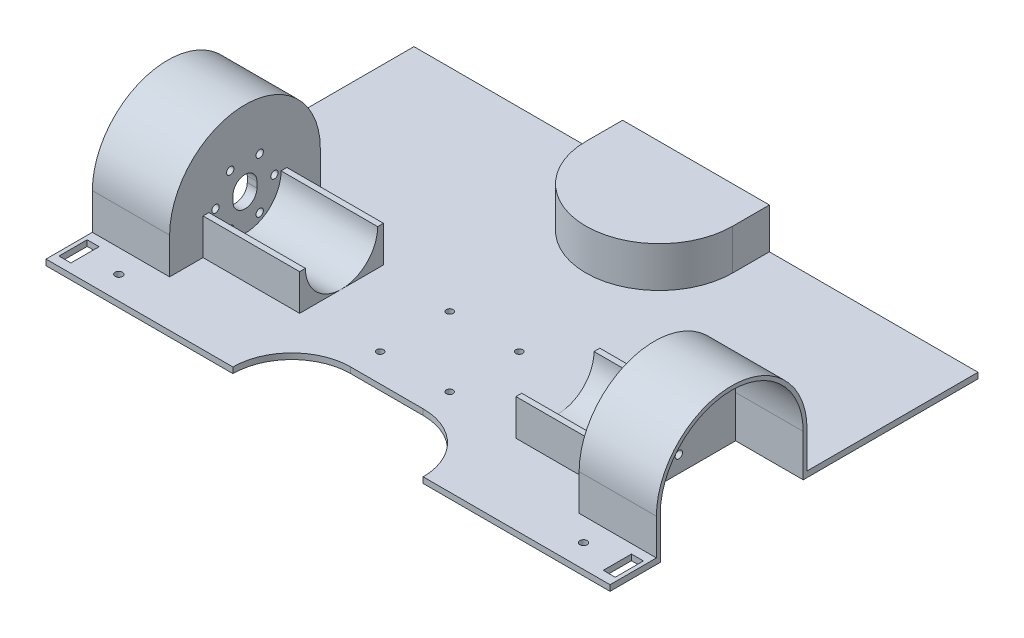
SolidWorks part; units mm, degrees
ref_plane "Front Plane" through (0, 0, 0) normal (0, 0, 1) x (1, 0, 0)
ref_plane "Top Plane" through (0, 0, 0) normal (0, 1, 0) x (1, 0, 0)
ref_plane "Right Plane" through (0, 0, 0) normal (1, 0, 0) x (0, 0, -1)
sketch3d "3DSketch1"
  line L0 (-150, -15, 34.5) -> (150, -15, 34.5) construction
  line L1 (150, -15, 34.5) -> (150, -15, -165.5) construction
  line L2 (150, -15, -165.5) -> (-150, -15, -165.5) construction
  line L3 (-150, -15, -165.5) -> (-150, -15, 34.5) construction
  line L4 (-150, -15, 34.5) -> (-150, 185, 34.5) construction
  line L5 (-150, 185, 34.5) -> (150, 185, 34.5) construction
  line L6 (150, 185, 34.5) -> (150, -15, 34.5) construction
  line L7 (0, -15, 0) -> (0, -15, 34.5) construction
  line L8 (150, 185, 34.5) -> (150, 185, -165.5) construction
  line L9 (150, 185, -165.5) -> (150, -15, -165.5) construction
  line L10 (150, 185, -165.5) -> (-150, 185, -165.5) construction
  line L11 (-150, 185, -165.5) -> (-150, -15, -165.5) construction
  line L12 (-150, 185, -165.5) -> (-150, 185, 34.5) construction
  line L13 (0, -15, 0) -> (0, 0, 0) construction
  dimension "D5" = 15
  dimension "D1" = 34.5
  dimension "D2" = 300
  dimension "D3" = 200
  dimension "D4" = 200
sketch "Sketch2" plane through (0, 0, 0) normal (0, 1, 0) x (1, 0, 0)
  line L0 (-146, 0) -> (146, 0)
  line L1 (146, 0) -> (146, 160)
  line L2 (146, 160) -> (-146, 160)
  line L3 (150, -34.5) -> (150, 165.5) construction
  line L4 (-146, 160) -> (-146, 0)
  line L5 (150, 165.5) -> (-150, 165.5) construction
  point P4 (0, 0)
  point P11 (0, 0)
  dimension "D1" = 4
  dimension "D2" = 5.5
extrude "Boss-Extrude1" add sketch "Sketch2" along normal blind 3
sketch "Sketch3" plane through (0, 3, 0) normal (0, 1, 0) x (1, 0, 0)
  line L0 (146, 0) -> (146, -30.5)
  line L1 (146, -30.5) -> (49.25, -30.5)
  line L2 (-146, 0) -> (146, 0) construction
  line L3 (-150, -34.5) -> (150, -34.5) construction
  line L4 (0, 0) -> (0, -34.5) construction
  line L5 (0, -110) -> (0, 110) construction
  line L6 (-146, -30.5) -> (-49.25, -30.5)
  line L7 (-146, 0) -> (-146, -30.5)
  arc A0 (49.25, -30.5) -> (18.75, 0) centre (18.75, -30.5) ccw
  arc A1 (-49.25, -30.5) -> (-18.75, 0) centre (-18.75, -30.5) cw
  line M4 (-146, 0) -> (146, 0)
  dimension "D1" = 4
  dimension "D2" = 18.75
extrude "Boss-Extrude2" add sketch "Sketch3" against normal up to surface (3 mm away) contours L6 A1 L7 M4 | A0 L1 L0 M4 region at (-94.128, 3, 14.7154) region at (94.128, 3, 14.7154) up to face at (0, 0, -80)
sketch "Sketch4" plane through (146, 0, 0) normal (1, 0, 0) x (0, 0, -1)
  line L0 (10.8, 3) -> (10.8, 21.7)
  line L1 (-30.5, 3) -> (160, 3) construction
  line L2 (10.8, 21.7) -> (13.8, 21.7)
  line L3 (51.2, 21.7) -> (54.2, 21.7)
  line L4 (54.2, 21.7) -> (54.2, 3)
  line L6 (-6.5, 3) -> (-6.5, 21.7) construction
  line L7 (-30.5, 0) -> (-30.5, 3) construction
  arc A0 (13.8, 21.7) -> (51.2, 21.7) centre (32.5, 21.7) ccw
  line M7 (160, 3) -> (-30.5, 3)
  dimension "D1" = 18.7
  dimension "D2" = 3
  dimension "D3" = 39
  dimension "D4" = 24
extrude "Boss-Extrude3" add sketch "Sketch4" against normal blind 55 from offset 35 contours A0 L2 L0 M7 | A0 L4 L3 M7 region at (146, 9.3899, -49.4515) region at (146, 9.3899, -15.5485) offset against normal yes
sketch "Sketch5" plane through (111, 0, 0) normal (1, 0, 0) x (0, 0, -1)
  line L0 (-4.5, 0) -> (-4.5, 21.7)
  line L1 (-30.5, 0) -> (160, 0) construction
  line L3 (69.5, 21.7) -> (69.5, 0)
  line L4 (71.5, 21.7) -> (71.5, 0)
  line L5 (-6.5, 0) -> (-6.5, 21.7)
  line L6 (71.5, 0) -> (-6.5, 0)
  line L7 (32.5, 23.2) -> (32.5, 20.2) construction
  line L8 (38.7, 23.2) -> (38.7, 20.2)
  line L9 (26.3, 23.2) -> (26.3, 20.2)
  circle A0 centre (32.5, 21.7) radius 21.7 construction
  circle A1 centre (32.5, 21.7) radius 37 construction
  arc A2 (-4.5, 21.7) -> (69.5, 21.7) centre (32.5, 21.7) cw
  arc A3 (-6.5, 21.7) -> (71.5, 21.7) centre (32.5, 21.7) cw
  arc A4 (38.7, 23.2) -> (26.3, 23.2) centre (32.5, 23.2) ccw
  arc A5 (26.3, 20.2) -> (38.7, 20.2) centre (32.5, 20.2) ccw
  circle A6 centre (17.25, 21.7) radius 1.9
  circle A7 centre (24.875, 34.9069) radius 1.9
  circle A8 centre (32.5, 21.7) radius 21.7 construction
  circle A9 centre (40.125, 34.9069) radius 1.9
  circle A10 centre (32.5, 21.7) radius 21.7 construction
  circle A11 centre (47.75, 21.7) radius 1.9
  circle A12 centre (32.5, 21.7) radius 21.7 construction
  circle A13 centre (40.125, 8.4931) radius 1.9
  circle A14 centre (32.5, 21.7) radius 21.7 construction
  circle A15 centre (24.875, 8.4931) radius 1.9
  circle A16 centre (32.5, 21.7) radius 21.7 construction
  point P19 (26.3, 21.7)
  point P20 (32.5, 21.7)
  arc M14 (51.2, 21.7) -> (32.5, 3) centre (32.5, 21.7) cw
  line M15 (32.5, 3) -> (54.2, 3)
  line M16 (54.2, 3) -> (54.2, 21.7)
  line M17 (54.2, 21.7) -> (51.2, 21.7)
  dimension "D1" = 74
  dimension "D5" = 3.8
  dimension "D3" = 12.4
  dimension "D4" = 3
  dimension "D6" = 15.25
  dimension "D7" = 6
extrude "Boss-Extrude4" add sketch "Sketch5" against normal blind 5 contours A2 L0 L6 L3 A15 A13 A11 A9 A7 A6 A5 L9 A4 L8 M14 M17 M16 M15 | A3 L5 L6 L0 A2 L3 L4 | M17 M14 M15 M16 region at (111, 0.9884, 5.5) region at (111, 10.85, 3.5555) region at (111, 9.3899, -49.4515)
extrude "Boss-Extrude5" add sketch "Sketch5<4>" along normal blind 35 contours A3 L5 L6 L0 A2 L3 L4 region at (111, 0.9884, 5.5)
sketch "Sketch5<4>" plane through (111, 0, 0) normal (1, 0, 0) x (0, 0, -1) same geometry as "Sketch5"
extrude "Cut-Extrude1" cut sketch "Sketch5<5>" along normal through all contours A2 L0 L6 L3 A15 A13 A11 A9 A7 A6 A5 L9 A4 L8 M14 M17 M16 M15 | M17 M14 M15 M16 region at (111, 10.85, 3.5555) region at (111, 9.3899, -49.4515)
sketch "Sketch5<5>" plane through (111, 0, 0) normal (1, 0, 0) x (0, 0, -1) same geometry as "Sketch5"
sketch "Sketch6" plane through (0, 3, 0) normal (0, 1, 0) x (1, 0, 0)
  line L0 (146, -30.5) -> (146, -6.5) construction
  line L1 (144, -11.2) -> (137.8, -11.2)
  line L2 (144, -11.2) -> (144, -25.8)
  line L3 (144, -25.8) -> (137.8, -25.8)
  line L4 (137.8, -11.2) -> (137.8, -25.8)
  circle A0 centre (120.3, -18.5) radius 1.9
  point P6 (146, -18.5)
  point P7 (144, -18.5)
  point P11 (137.8, -18.5)
  dimension "D5" = 3.8
  dimension "D2" = 14.6
  dimension "D3" = 6.2
  dimension "D4" = 17.5
extrude "Cut-Extrude2" cut sketch "Sketch6" against normal through all
mirror "Mirror1" about plane through (0, 0, 0) normal (1, 0, 0) of "Cut-Extrude2", "Cut-Extrude1", "Boss-Extrude5", "Boss-Extrude4", "Boss-Extrude3"
sketch "Sketch7" plane through (0, 3, 0) normal (0, 1, 0) x (1, 0, 0)
  line L1 (-18, 14.5) -> (18, 14.5) construction
  line L2 (-18, 14.5) -> (-18, 50.5) construction
  line L3 (-18, 50.5) -> (18, 50.5) construction
  line L4 (18, 14.5) -> (18, 50.5) construction
  circle A0 centre (-18, 14.5) radius 1.75
  circle A1 centre (18, 14.5) radius 1.75
  circle A2 centre (18, 50.5) radius 1.75
  circle A3 centre (-18, 50.5) radius 1.75
  point P4 (0, 14.5)
  point P10 (-18, 32.5)
  dimension "D3" = 3.5
  dimension "D1" = 36
  dimension "D2" = 36
extrude "Cut-Extrude3" cut sketch "Sketch7" against normal through all
ref_plane "Plane1" through (0, 21, 0) normal (0, 1, 0) x (1, 0, 0)
sketch "Sketch8" plane through (0, 21, 0) normal (0, 1, 0) x (1, 0, 0)
  line L0 (146, 160) -> (-146, 160) construction
  line L1 (-16, 160) -> (16, 160)
  line L2 (-16, 160) -> (-16, 122)
  line L3 (-16, 122) -> (16, 122)
  line L4 (16, 160) -> (16, 122)
  line L5 (-35, 141) -> (-35, 160)
  line L6 (35, 141) -> (35, 160)
  line L7 (-35, 160) -> (35, 160)
  arc A0 (-35, 141) -> (35, 141) centre (0, 141) ccw
  point P6 (0, 122)
  point P10 (-16, 141)
  dimension "D1" = 32
  dimension "D2" = 38
  dimension "D3" = 70
extrude "Boss-Extrude6" add sketch "Sketch8" along normal blind 3 separate body contours L4 L1 L2 L3 | L3 region at (0, 21, -141) region at (-16.8841, 21, -141)
sketch "Sketch10" plane through (0, 24, 0) normal (0, 1, 0) x (1, 0, 0)
  line L0 (38, 141) -> (38, 160)
  line L2 (-38, 160) -> (-38, 141)
  line L3 (35, 141) -> (35, 160)
  line L4 (35, 160) -> (-35, 160)
  line L5 (-35, 160) -> (-35, 141)
  line L6 (35, 141) -> (35, 160)
  line L7 (35, 160) -> (-35, 160)
  line L8 (-35, 160) -> (-35, 141)
  line L9 (38, 163) -> (-38, 163) construction
  line L10 (-35, 160) -> (-38, 160)
  line L11 (35, 160) -> (38, 160)
  line L12 (146, 160) -> (-146, 160) construction
  line L13 (-38, 163) -> (-38, 141) construction
  line L14 (38, 141) -> (38, 163) construction
  arc A0 (-38, 141) -> (38, 141) centre (0, 141) ccw
  arc A1 (-35, 141) -> (35, 141) centre (0, 141) ccw
  arc A2 (-35, 141) -> (35, 141) centre (0, 141) ccw
  line M5 (35, 141) -> (35, 160)
  line M7 (-35, 160) -> (-35, 141)
  arc M8 (-35, 141) -> (35, 141) centre (0, 141) ccw
  dimension "D1" = 0
  dimension "D2" = 3
extrude "Boss-Extrude7" add sketch "Sketch10" against normal up to surface (21 mm away) contours L2 A0 L0 L11 L10 M5 M8 M7 region at (0, 24, -103.95) up to face at (-18, 3, -48.75)
extrude "Cut-Extrude4" cut sketch "Sketch8<3>" against normal through all contours L4 L1 L2 L3 | L5 A0 L6 L7 L4 L3 L2 region at (0, 21, -141) region at (-16.8841, 21, -141)
sketch "Sketch8<3>" plane through (0, 21, 0) normal (0, 1, 0) x (1, 0, 0) same geometry as "Sketch8"
equation "\"h\"= 15mm"
equation "\"espacio_longitudinal_griper\"= 34.5mm"
equation "\"D5@3DSketch1\"=\"h\""
equation "\"D1@3DSketch1\"=\"espacio_longitudinal_griper\""
equation "\"t\"= 3mm"
equation "\"toleracia_distacia_max\"= 1mm"
equation "\"D1@Sketch2\"=\"t\"+\"toleracia_distacia_max\""
equation "\"D2@Sketch2\"=\"t\"+2.5 * \"toleracia_distacia_max\""
equation "\"D1@Boss-Extrude1\"=\"t\""
equation "\"D1@Sketch3\"=\"toleracia_distacia_max\"+\"t\""
equation "\"D2@Sketch4\"=\"t\""
equation "\"M3_CT\"= 3.8mm'M3+una tolerancial por impresion"
equation "\"D5@Sketch5\"=\"M3_CT\""
equation "\"D5@Sketch6\"=\"M3_CT\""
equation "\"D1@Boss-Extrude6\"=\"t\""
